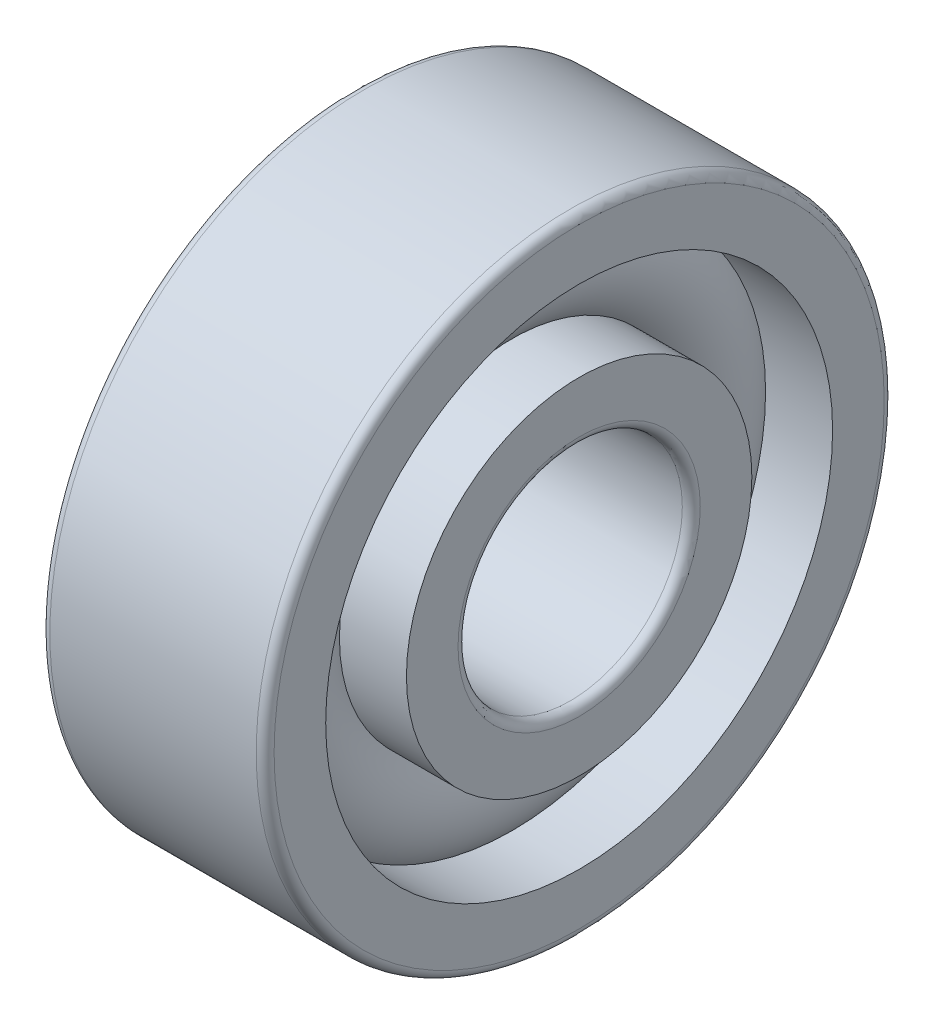
SolidWorks part; units mm, degrees
ref_plane "Plane1" through (0, 0, 0) normal (0, 0, 1) x (1, 0, 0)
ref_plane "Plane2" through (0, 0, 0) normal (0, 1, 0) x (1, 0, 0)
ref_plane "Plane3" through (0, 0, 0) normal (1, 0, 0) x (0, 0, -1)
other "Configuration Table"
sketch "Clipboard" plane through (0, 0, 0) normal (0, 0, 1) x (1, 0, 0)
  line L0 (-10, 0) -> (10, 0) construction
  line L1 (0, 0) -> (22.3471, -0.7804)
  line L2 (0, 0) -> (4.7471, 0.1658)
  line L3 (0, 0) -> (22.3471, -0.7804)
  line L4 (0, 0) -> (-22.3573, -0.3902)
  dimension "BallCLRad" = 4.75
sketch "CagSpiSke" plane through (0, 0, 0) normal (0, 0, 1) x (1, 0, 0)
  line L0 (0.135, 4.525) -> (0.135, 4.975)
  line L1 (0.135, 4.975) -> (-0.135, 4.975)
  line L2 (-0.135, 4.975) -> (-0.135, 4.525)
  line L3 (-0.135, 4.525) -> (0.135, 4.525)
  line L4 (-20.6375, 0) -> (20.6375, 0) construction
  line L5 (0, 0) -> (0, 23.7692) construction
  dimension "OD" = 9.95
  dimension "ID" = 9.05
revolve "CageSpine" add sketch "CagSpiSke" angle 0.001 about L4 reverse direction yes
ref_axis "Axis1" through (-50, 0, 0) along (1, 0, 0)
sketch "CagBalSke" plane through (0, 0, 0) normal (0, 0, 1) x (1, 0, 0)
  line L0 (-1.485, 4.75) -> (1.485, 4.75)
  line L1 (-1.905, 4.75) -> (1.905, 4.75) construction
  line L2 (-10, 0) -> (10, 0) construction
  line L3 (0, 0) -> (0, 24) construction
  arc A0 (1.485, 4.75) -> (-1.485, 4.75) centre (0, 4.75) cw
  dimension "BallCLRad" = 4.75
revolve "CageBall" [suppressed] add sketch "CagBalSke" angle 360 about L1 reverse direction yes
pattern_circular "CageBalls" [suppressed] count 2 every 180 about axis through (-50, 0, 0) along (1, 0, 0)
sketch "CagTrmODSke" plane through (0, 0, 0) normal (0, 0, 1) x (1, 0, 0)
  line L0 (1.486, 4.975) -> (1.486, 6.236)
  line L1 (1.486, 6.236) -> (-1.486, 6.236)
  line L2 (-1.486, 6.236) -> (-1.486, 4.975)
  line L3 (-1.486, 4.975) -> (1.486, 4.975)
  line L4 (-20.6375, 0) -> (20.6375, 0) construction
  line L5 (0, 0) -> (0, 25) construction
  dimension "Width" = 2.972
  dimension "ID" = 9.95
  dimension "OD" = 12.472
revolve "CageTrimOD" [suppressed] cut sketch "CagTrmODSke" angle 360 about L4 reverse direction yes
sketch "CagTrmIDSke" plane through (0, 0, 0) normal (0, 0, 1) x (1, 0, 0)
  line L0 (1.486, 3.266) -> (1.486, 4.525)
  line L1 (1.486, 4.525) -> (-1.486, 4.525)
  line L2 (-1.486, 4.525) -> (-1.486, 3.266)
  line L3 (-1.486, 3.266) -> (1.486, 3.266)
  line L4 (-20.6375, 0) -> (20.6375, 0) construction
  line L5 (0, 0) -> (0, 25) construction
  dimension "Width" = 2.972
  dimension "ID" = 6.532
  dimension "OD" = 9.05
revolve "CageTrimID" [suppressed] cut sketch "CagTrmIDSke" angle 360 about L4 reverse direction yes
sketch "BalSimSke" plane through (0, 0, 0) normal (0, 0, 1) x (1, 0, 0)
  line L0 (-10, 0) -> (10, 0) construction
  line L1 (-10, 4.75) -> (10, 4.75) construction
  line L2 (0, 0) -> (0, 23) construction
  circle A0 centre (0, 4.75) radius 1.35
  dimension "BallCLRad" = 4.75
  dimension "Ball_diameter" = 2.7
revolve "BallsSimplified" add sketch "BalSimSke" angle 360 about L0
sketch "BalDetSke" plane through (0, 0, 0) normal (0, 0, 1) x (1, 0, 0)
  line L0 (-1.35, 4.75) -> (1.35, 4.75)
  line L1 (-1.905, 4.75) -> (1.905, 4.75) construction
  line L2 (0, 0) -> (0, 25) construction
  arc A0 (1.35, 4.75) -> (-1.35, 4.75) centre (0, 4.75) cw
  dimension "BallCLRad" = 4.75
  dimension "Ball_diameter" = 2.7
revolve "BallDetailed" [suppressed] add sketch "BalDetSke" angle 360 about L1 reverse direction yes
sketch "InnRacSke" plane through (0, 0, 0) normal (0, 0, 1) x (1, 0, 0)
  line L0 (-0.9724, 3.85) -> (-2.5, 3.85)
  line L1 (-2.5, 3.85) -> (-2.5, 2.7)
  line L2 (-2.3, 2.5) -> (2.3, 2.5)
  line L3 (2.5, 2.7) -> (2.5, 3.85)
  line L4 (2.5, 3.85) -> (0.9724, 3.85)
  line L5 (-20.6375, 0) -> (20.6375, 0) construction
  line L6 (0, 0) -> (0, 30) construction
  arc A0 (-2.5, 2.7) -> (-2.3, 2.5) centre (-2.3, 2.7) ccw
  arc A1 (2.3, 2.5) -> (2.5, 2.7) centre (2.3, 2.7) ccw
  arc A2 (0.9724, 3.85) -> (-0.9724, 3.85) centre (0, 4.75) cw
  dimension "BallCLRad" = 4.75
  dimension "Fillet_radius" = 0.2
  dimension "Ball_diameter" = 2.65
  dimension "ID" = 5
  dimension "OD" = 7.7
  dimension "Width" = 5
revolve "InnerRace" add sketch "InnRacSke" angle 360 about L5 reverse direction yes
sketch "OutRacSke" plane through (0, 0, 0) normal (0, 0, 1) x (1, 0, 0)
  line L0 (-0.9724, 5.65) -> (-2.5, 5.65)
  line L1 (-2.5, 5.65) -> (-2.5, 6.8)
  line L2 (-2.3, 7) -> (2.3, 7)
  line L3 (2.5, 6.8) -> (2.5, 5.65)
  line L4 (2.5, 5.65) -> (0.9724, 5.65)
  line L5 (-20.6375, 0) -> (20.6375, 0) construction
  line L6 (0, 0) -> (0, 30) construction
  arc A0 (-2.5, 6.8) -> (-2.3, 7) centre (-2.3, 6.8) cw
  arc A1 (2.3, 7) -> (2.5, 6.8) centre (2.3, 6.8) cw
  arc A2 (0.9724, 5.65) -> (-0.9724, 5.65) centre (0, 4.75) ccw
  dimension "BallCLRad" = 4.75
  dimension "Fillet_radius" = 0.2
  dimension "Ball_diameter" = 2.65
  dimension "Width" = 5
revolve "OuterRace" add sketch "OutRacSke" angle 360 about L5 reverse direction yes
pattern_circular "BallsDetailed" [suppressed] count 2 every 180 about axis through (-50, 0, 0) along (1, 0, 0)
equation "\"BallCLRad@Clipboard\" = ( \"OD@OutRacSke\" + \"ID@InnRacSke\" ) / 4"
equation "\"BallCLRad@BalSimSke\" = \"BallCLRad@Clipboard\""
equation "\"BallCLRad@BalDetSke\" = \"BallCLRad@Clipboard\""
equation "\"BallCLRad@InnRacSke\" = \"BallCLRad@Clipboard\""
equation "\"BallCLRad@OutRacSke\" = \"BallCLRad@Clipboard\""
equation "\"Ball_diameter@InnRacSke\" = \"Ball_diameter@BalDetSke\" - 0.05"
equation "\"Ball_diameter@OutRacSke\" = \"Ball_diameter@BalDetSke\" - 0.05"
equation "\"Ball_diameter@BalSimSke\" = \"Ball_diameter@BalDetSke\""
equation "\"Width@OutRacSke\" = \"Width@InnRacSke\""
equation "\"Fillet_radius@OutRacSke\" = \"Fillet_radius@InnRacSke\""
equation "\"Max_count@Clipboard\" = int( 3.14159265 / atn(( \"Ball_diameter@BalDetSke\" / 2) / sqr( \"BallCLRad@Clipboard\"  *  \"BallCLRad@Clipboard\" - ( \"Ball_diameter@BalDetSke\" / 2) *  ( \"Ball_diameter@BalDetSke\" / 2))))"
equation "\"Max_count@Clipboard\" = ((sgn( \"Max_count@Clipboard\" - \"Count@Clipboard\" )-1)*( \"Max_count@Clipboard\" - \"Count@Clipboard\" ))/-2+ \"Count@Clipboard\""
equation "\"Count@BallsDetailed\" = int( \"Show_count@Clipboard\" ) "
equation "\"Count@BallsDetailed\" = ((sgn( \"Count@BallsDetailed\" - \"Max_count@Clipboard\" )-1)*( \"Count@BallsDetailed\" - \"Max_count@Clipboard\" ))/-2+ \"Max_count@Clipboard\""
equation "\"Count@BallsDetailed\" = ((sgn( \"Count@BallsDetailed\" - \"Min_count@Clipboard\" )+1)*( \"Count@BallsDetailed\" - \"Min_count@Clipboard\"))/2 +\"Min_count@Clipboard\""
equation "\"Angle@BallsDetailed\" = 360.0 / \"Max_count@Clipboard\""
equation "\"BallCLRad@CagBalSke\" = \"BallCLRad@Clipboard\""
equation "\"Count@CageBalls\" = \"Count@BallsDetailed\""
equation "\"Angle@CageBalls\" = \"Angle@BallsDetailed\""
equation "\"Angle@CageSpine\" =  \"Angle@CageBalls\" * ( \"Count@CageBalls\" -1 + int( \"Count@CageBalls\" / \"Max_count@Clipboard\" ) )  + 0.001 -  int( \"Count@CageBalls\" / \"Max_count@Clipboard\" ) * 0.001"
equation "\"Angle@CageSpine\" =  \"Angle@CageSpine\" * int( \"Min_count@Clipboard\" / 2) + int(1 / \"Min_count@Clipboard\")  * 0.001"
equation "\"CageWallOD@CagBalSke\" =  \"Ball_diameter@BalDetSke\" * 1.1"
equation "\"Thickness@CagSpiSke\" =  \"Ball_diameter@BalDetSke\" * 0.1"
equation "\"OD@CagTrmODSke\" = \"BallCLRad@Clipboard\" * 2 + \"CageWallOD@CagBalSke\" + 0.002"
equation "\"ID@CagTrmODSke\" = \"BallCLRad@Clipboard\" * 2 + \"Ball_diameter@BalDetSke\" / 6"
equation "\"OD@CagTrmIDSke\" = \"BallCLRad@Clipboard\" * 2 - \"Ball_diameter@BalDetSke\" / 6"
equation "\"ID@CagTrmIDSke\" = \"BallCLRad@Clipboard\" * 2 - \"CageWallOD@CagBalSke\" + 0.002"
equation "\"OD@CagSpiSke\" = \"ID@CagTrmODSke\""
equation "\"ID@CagSpiSke\" = \"OD@CagTrmIDSke\""
equation "\"Width@CagTrmODSke\" = \"CageWallOD@CagBalSke\" + 0.002"
equation "\"Width@CagTrmIDSke\" = \"CageWallOD@CagBalSke\" + 0.002"
